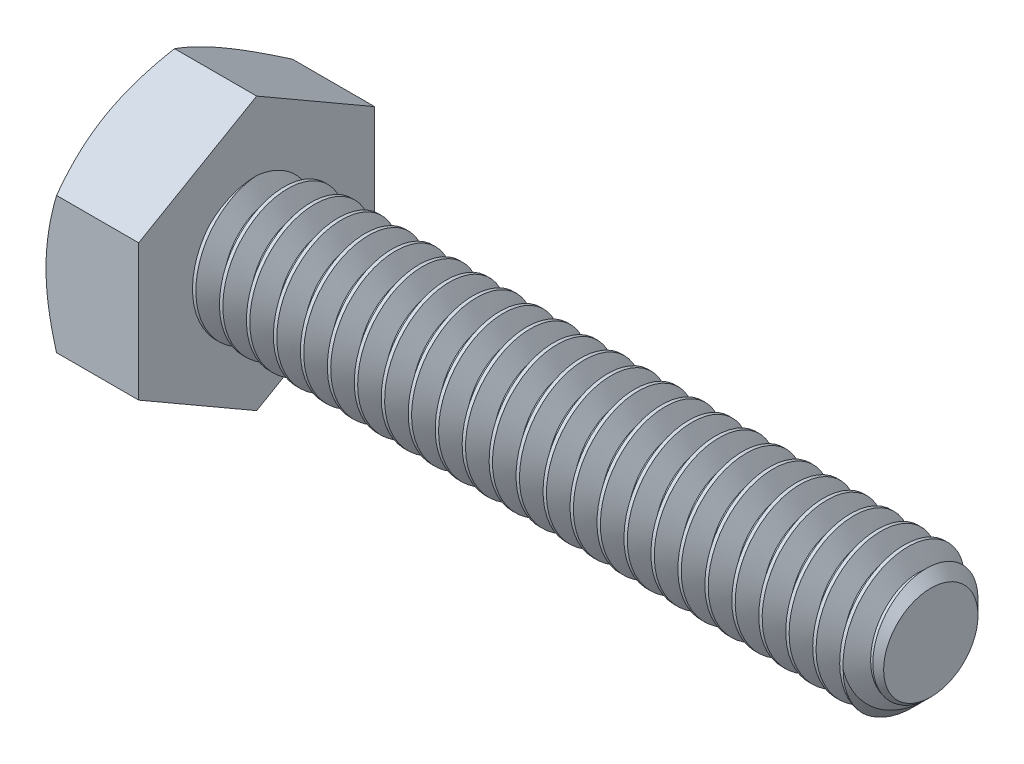
SolidWorks part; units mm, degrees
note: '?' marks a value the reader was unsure of.
ref_plane "Front Plane" through (0, 0, 0) normal (0, 0, 1) x (1, 0, 0)
ref_plane "Top Plane" through (0, 0, 0) normal (0, 1, 0) x (1, 0, 0)
ref_plane "Right Plane" through (0, 0, 0) normal (1, 0, 0) x (0, 0, -1)
sketch "Sketch1" plane through (0, 0, 0) normal (0, 0, 1) x (1, 0, 0)
  line L0 (-18.0578, 0) -> (18.0578, 0) construction
  line L1 (18.0578, 3.175) -> (18.0578, -3.175) construction
  line L2 (-13.6922, 5.5562) -> (-13.6922, -5.5562) construction
  line L3 (-18.0578, 5.5562) -> (-18.0578, -5.5562) construction
  point P9 (-13.6922, 0)
  point P10 (13.6128, -3.175)
  dimension "D1" = 4.445
  dimension "Screw Dia" = 6.35
  dimension "Hex" = 11.1125
  dimension "Head Ht" = 4.3656
  dimension "Screw Lenght" = 31.75
ref_plane "Plane2" through (18.0578, 0, 0) normal (1, 0, 0) x (0, 0, -1)
sketch "Sketch5" plane through (18.0578, 0, 0) normal (1, 0, 0) x (0, 0, -1)
  circle A0 centre (0, 0) radius 3.175
extrude "Boss-Extrude3" add sketch "Sketch5" against normal up to vertex (31.75 mm away) up to point (-13.6922, 0, 0)
sketch "Sketch9" plane through (18.0578, 0, 0) normal (1, 0, 0) x (0, 0, -1)
  circle A1 centre (0, 0) radius 3.175
  circle A2 centre (0, 0) radius 3.175
  dimension "D1" = 0
curve "Helix/Spiral1" pitch 1.27 height 33.02 turns 26 parameters "Pitch"=1.27
chamfer "Chamfer1" distance 0.9525 angle 45 1 edges at (18.0578, 0, -3.175)
sketch "Sketch10" plane through (0, 0, 0) normal (0, 0, 1) x (1, 0, 0)
  line L0 (18.0578, 3.175) -> (18.5341, 2.3501)
  line L1 (18.5341, 2.3501) -> (18.6928, 2.3501)
  line L2 (18.6928, 2.3501) -> (19.1691, 3.175)
  line L3 (18.0578, 3.175) -> (19.1691, 3.175)
  line L4 (18.6134, 3.175) -> (18.6134, 2.3501) construction
  line L5 (18.2959, 2.7626) -> (18.9309, 2.7626) construction
  dimension "D1" = 60
  dimension "D2" = 0.1588
  dimension "D3" = 0.635
sweep "Cut-Sweep1" cut profiles "Sketch10" path "Helix/Spiral1"
sketch "Sketch6" plane through (-13.6922, 0, 0) normal (-1, 0, 0) x (0, 0, 1)
  line L0 (0, 5.5562) -> (0, -5.5562) construction
  line L1 (5.5562, 3.2079) -> (0, 6.4158)
  line L2 (0, 6.4158) -> (-5.5563, 3.2079)
  line L3 (-5.5563, 3.2079) -> (-5.5563, -3.2079)
  line L4 (-5.5563, -3.2079) -> (0, -6.4158)
  line L5 (0, -6.4158) -> (5.5562, -3.2079)
  line L6 (5.5562, -3.2079) -> (5.5562, 3.2079)
  circle A0 centre (0, 0) radius 5.5562 construction
extrude "Boss-Extrude4" add sketch "Sketch6" along normal up to vertex (4.3656 mm away) up to point (-18.0578, -5.5562, 0)
sketch "Sketch7" plane through (-18.0578, 0, 0) normal (-1, 0, 0) x (0, 0, 1)
  circle A0 centre (0, 0) radius 5.5562 construction
  circle A1 centre (0, 0) radius 5.5562
sketch "Sketch8" plane through (-18.0578, 0, 0) normal (-1, 0, 0) x (0, 0, 1)
  circle A0 centre (0, 0) radius 5.5562 construction
  circle A1 centre (0, 0) radius 5.5562
extrude "Cut-Extrude3" cut sketch "Sketch8" against normal through all draft 60 flip side to cut
sketch "Sketch12" plane through (-18.0578, 0, 0) normal (-1, 0, 0) x (0, 0, 1)
  line L0 (0, 4.2783) -> (0, 2.3892) construction
  line L1 (0.1667, 4.2783) -> (0.1667, 2.3892)
  line L2 (-0.1667, 4.2783) -> (-0.1667, 2.3892)
  line L3 (0, 3.175) -> (0, -3.175) construction
  arc A0 (0.1667, 4.2783) -> (-0.1667, 4.2783) centre (0, 4.2783) ccw
  arc A1 (-0.1667, 2.3892) -> (0.1667, 2.3892) centre (0, 2.3892) ccw
  circle A3 centre (0, 0) radius 2.2225 construction
  circle A4 centre (0, 0) radius 4.445 construction
  point P2 (0, 3.3337)
  dimension "D1" = 4.445
  dimension "D3" = 8.89
  dimension "D2" = 0.3334
extrude "Cut-Extrude4" cut sketch "Sketch12" against normal blind 0.254
pattern_circular "CirPattern1" count 6 over 360 about axis through (0, 0, 0) along (1, 0, 0) of "Cut-Extrude4"
ref_axis "Axis1" through (0, 0, 0) along (1, 0, 0)?
equation "\"D2@Sketch10\" = \"Pitch@Helix/Spiral1\"*.125"
equation "\"D3@Sketch10\" = \"Pitch@Helix/Spiral1\"*.5"
equation "\"D3@Helix/Spiral1\" = \"Screw Lenght@Sketch1\"+\"Pitch@Helix/Spiral1\""
equation "\"D1@Chamfer1\" = \"Pitch@Helix/Spiral1\"*.75"
equation "\"D1@Sketch12\" = \"Hex@Sketch1\"*.4"
equation "\"D3@Sketch12\" = \"Hex@Sketch1\"*.8"
equation "\"D2@Sketch12\" = \"Hex@Sketch1\"*.03"
equation "\"D1@Sketch1\" = \"Pitch@Helix/Spiral1\"*3.5"
